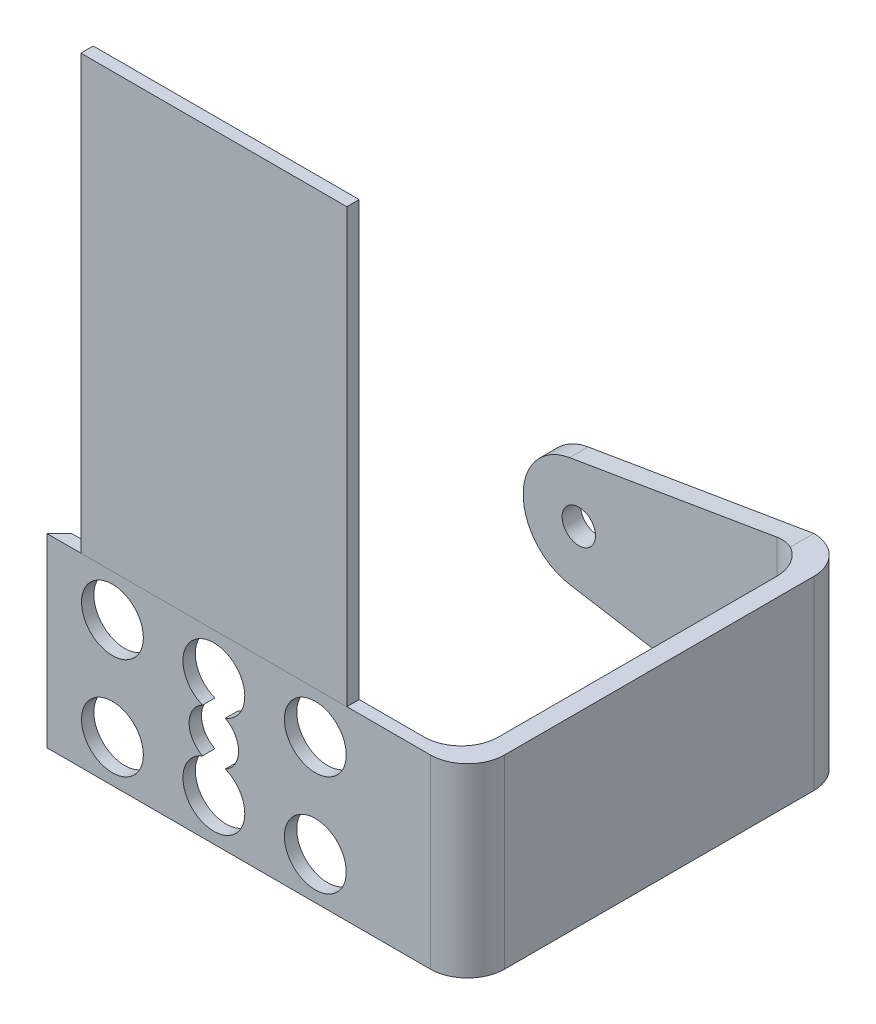
SolidWorks part; units mm, degrees
ref_plane "前视基准面" through (0, 0, 0) normal (0, 0, 1) x (1, 0, 0)
ref_plane "上视基准面" through (0, 0, 0) normal (0, 1, 0) x (1, 0, 0)
ref_plane "右视基准面" through (0, 0, 0) normal (1, 0, 0) x (0, 0, -1)
sketch "草图1" plane through (0, 0, 0) normal (0, 0, 1) x (1, 0, 0)
  line L1 (-13.5, -7.5) -> (13.5, -7.5)
  line L2 (-13.5, -7.5) -> (-13.5, 7.5)
  line L3 (-13.5, 7.5) -> (13.5, 7.5)
  line L4 (13.5, -7.5) -> (13.5, 7.5)
  line L5 (-13.5, -7.5) -> (13.5, 7.5) construction
  line L6 (-13.5, 7.5) -> (13.5, -7.5) construction
  point P0 (0, 0)
  dimension "D1" = 27
  dimension "D2" = 15
extrude "凸台-拉伸1" add sketch "草图1" along normal blind 1
sketch "草图2" plane through (0, 0, 1) normal (0, 0, 1) x (1, 0, 0)
  line L0 (-8.2, 4.1) -> (8.2, 4.1) construction
  line L3 (0, 1.6) -> (0, -1.6) construction
  line L4 (8.2, 4.1) -> (8.2, -4.1) construction
  line L5 (8.2, -4.1) -> (-8.2, -4.1) construction
  line L6 (-8.2, -4.1) -> (-8.2, 4.1) construction
  circle A0 centre (0, 4.1) radius 2.5
  circle A1 centre (0, -4.1) radius 2.5
  circle A2 centre (8.2, 4.1) radius 2.5
  circle A3 centre (8.2, -4.1) radius 2.5
  circle A4 centre (-8.2, 4.1) radius 2.5
  circle A5 centre (-8.2, -4.1) radius 2.5
  point P2 (0, 1.6)
  point P5 (0, -1.6)
  point P6 (0, 0)
  point P11 (-2.5, 4.1)
  point P20 (-5.7, 4.1)
  dimension "D1" = 5
  dimension "D4" = 3.2
  dimension "D2" = 3.2
extrude "切除-拉伸1" cut sketch "草图2" against normal through all
sketch "草图3" plane through (0, -7.5, 0) normal (0, -1, 0) x (1, 0, 0)
  line L0 (13.5, 0) -> (19, 0)
  line L1 (13.5, 1) -> (13.5, 0)
  line L2 (20.5, 1) -> (13.5, 1)
  line L3 (20.5, 1) -> (20.5, -30)
  line L5 (19, -28.5) -> (19, 0)
  line L6 (-4.5, -28.5) -> (-4.5, -30)
  line L7 (-4.5, -30) -> (20.5, -30)
  line L9 (-4.5, -28.5) -> (19, -28.5)
  dimension "D1" = 7
  dimension "D2" = 1.5
  dimension "D3" = 1.5
  dimension "D4" = 30
  dimension "D5" = 25
extrude "凸台-拉伸2" add sketch "草图3" against normal up to surface (15 mm away) up to face at (0, 7.5, 0.5)
sketch "草图6" plane through (0, 0, 0) normal (0, 1, 0) x (1, 0, 0)
  line L0 (19, 0) -> (19, 5)
  line L1 (19, 28.5) -> (19, 0) construction
  line L2 (19, 5) -> (14, 0)
  line L3 (19, 0) -> (-13.5, 0) construction
  line L4 (14, 0) -> (19, 0)
  line L5 (19, 28.5) -> (14, 28.5)
  line L6 (-4.5, 28.5) -> (19, 28.5) construction
  line L7 (14, 28.5) -> (19, 23.5)
  line L8 (19, 23.5) -> (19, 28.5)
  line L9 (20.5, 30) -> (-4.5, 30) construction
  line L10 (19, 19) -> (17.5, 19)
  line L11 (19, 19) -> (19, 21)
  line L12 (19, 21) -> (17.5, 21)
  line L13 (17.5, 19) -> (17.5, 21)
  point P18 (17.5, 20)
  dimension "D1" = 5
  dimension "D2" = 5
  dimension "D3" = 5
  dimension "D4" = 5
  dimension "D5" = 10
  dimension "D6" = 1.5
  dimension "D7" = 2
extrude "凸台-拉伸3" add sketch "草图6" along normal mid plane 4
sketch "草图7" plane through (0, 0, -30) normal (0, 0, -1) x (-1, 0, 0)
  circle A0 centre (0, 0) radius 1.35
chamfer "倒角1" distance 1 angle 45 1 edges at (-13.5, 0, 0)
sketch "草图8" plane through (0, 0, 0) normal (0, 0, -1) x (-1, 0, 0)
  circle A0 centre (0, 0) radius 2
  dimension "D1" = 4
extrude "切除-拉伸4" cut sketch "草图8" against normal up to next
sketch "草图9" plane through (0, 0, 1) normal (0, 0, 1) x (1, 0, 0)
  line L0 (0, 0) -> (0, 32.1698) construction
  line L1 (20.5, 7.5) -> (-13.5, 7.5) construction
  line L2 (10.75, 42.5) -> (-10.75, 42.5)
  line L3 (10.75, 42.5) -> (10.75, 7.5)
  line L4 (10.75, 7.5) -> (-10.75, 7.5)
  line L5 (-10.75, 42.5) -> (-10.75, 7.5)
  line L6 (10.75, 42.5) -> (-10.75, 7.5) construction
  line L7 (10.75, 7.5) -> (-10.75, 42.5) construction
  point P3 (0, 25)
  dimension "D1" = 35
  dimension "D2" = 21.5
extrude "凸台-拉伸4" add sketch "草图9" against normal up to surface (1 mm away) separate body up to face at (0, 0, 0)
ref_plane "基准面1" through (0, 18.0524, 21.514) normal (0, 0.6428, 0.766) x (-1, 0, 0)
extrude "切除-拉伸5" cut sketch "草图7" against normal blind 10
fillet "圆角1" radius 3 6 edges at (20.5, 0, -30) (20.5, 0, 1) (19, 4.75, 0) (19, -4.75, 0) (19, 4.75, -28.5) (19, -4.75, -28.5)
sketch "草图10" plane through (0, 0, -30) normal (0, 0, -1) x (-1, 0, 0)
  line L0 (0.7448, 4.4379) -> (-17.5, 7.5)
  line L1 (-17.5, 7.5) -> (-17.5, -7.5)
  line L2 (-17.5, -7.5) -> (0.7448, -4.4379)
  line L3 (-17.5, 7.5) -> (4.5, 7.5)
  line L5 (4.5, 7.5) -> (4.5, -7.5)
  line L6 (4.5, -7.5) -> (-17.5, -7.5)
  circle A0 centre (0, 0) radius 4.5
  line M5 (4.5, 7.5) -> (-17.5, 7.5)
  line M7 (-17.5, -7.5) -> (4.5, -7.5)
  line M8 (4.5, -7.5) -> (4.5, 7.5)
extrude "切除-拉伸6" cut sketch "草图10" against normal up to next contours A0 L5 L0 M5 | A0 L2 M7 M8
